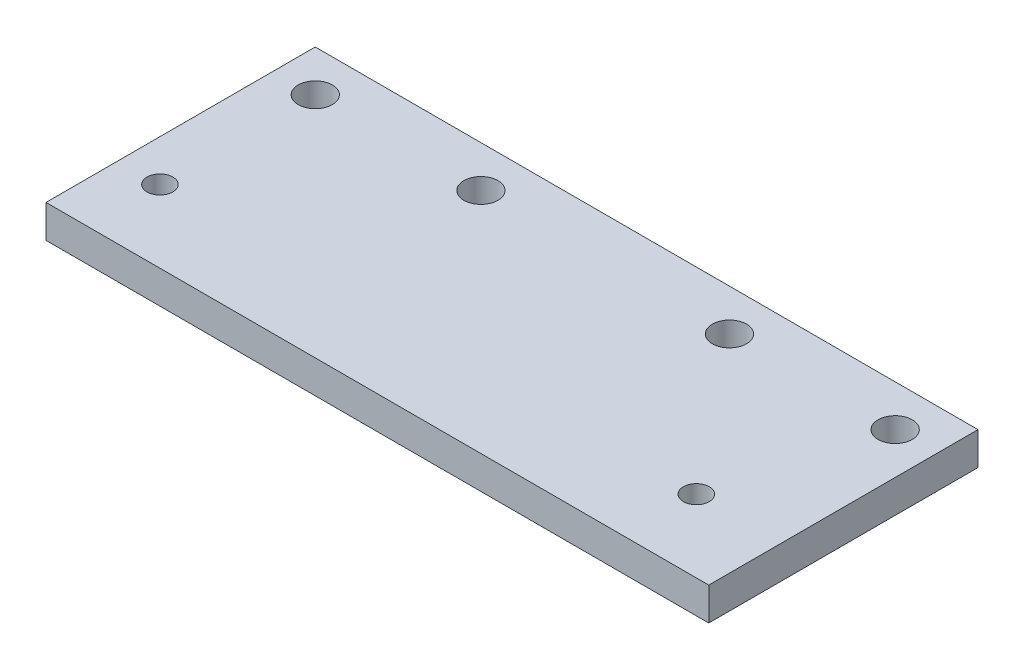
SolidWorks part; units mm, degrees
ref_plane "Front" through (0, 0, 0) normal (0, 0, 1) x (1, 0, 0)
ref_plane "Top" through (0, 0, 0) normal (0, 1, 0) x (1, 0, 0)
ref_plane "Right" through (0, 0, 0) normal (1, 0, 0) x (0, 0, -1)
sketch "Sketch1" plane through (0, 0, 0) normal (0, 1, 0) x (1, 0, 0)
  line L0 (0, 14) -> (64, 14)
  line L1 (0, 0) -> (64, 0)
  line L2 (0, 0) -> (0, 26)
  line L3 (0, 26) -> (64, 26)
  line L4 (64, 0) -> (64, 26)
  line L5 (0, 22) -> (64, 22)
  line L6 (0, 14) -> (0, 0)
  line L7 (0, 7) -> (4, 7)
  line L8 (64, 7) -> (55.8, 7)
  circle A0 centre (4, 22) radius 1.65
  circle A1 centre (20, 22) radius 1.65
  circle A2 centre (60, 22) radius 1.65
  circle A3 centre (44, 22) radius 1.65
  circle A4 centre (4, 7) radius 1.25
  circle A5 centre (55.8, 7) radius 1.25
  dimension "D6" = 3.3
  dimension "D8" = 3.3
  dimension "D10" = 3.3
  dimension "D11" = 16
  dimension "D13" = 8.2
  dimension "D1" = 12
  dimension "D2" = 14
  dimension "D3" = 4
  dimension "D4" = 64
  dimension "D5" = 4
  dimension "D7" = 4
  dimension "D9" = 16
  dimension "D12" = 4
extrude "Boss-Extrude1" add sketch "Sketch1" along normal blind 3.175 contours L1 L4 L0 L2 | A3 L5 A2 L4 L3 L2 A0 A1 | A3 L5 A1 A0 L2 L0 L4 A2 region at (32, 0, -17.8859) region at (32.0233, 0, -7) region at (32, 0, -24.0931)
